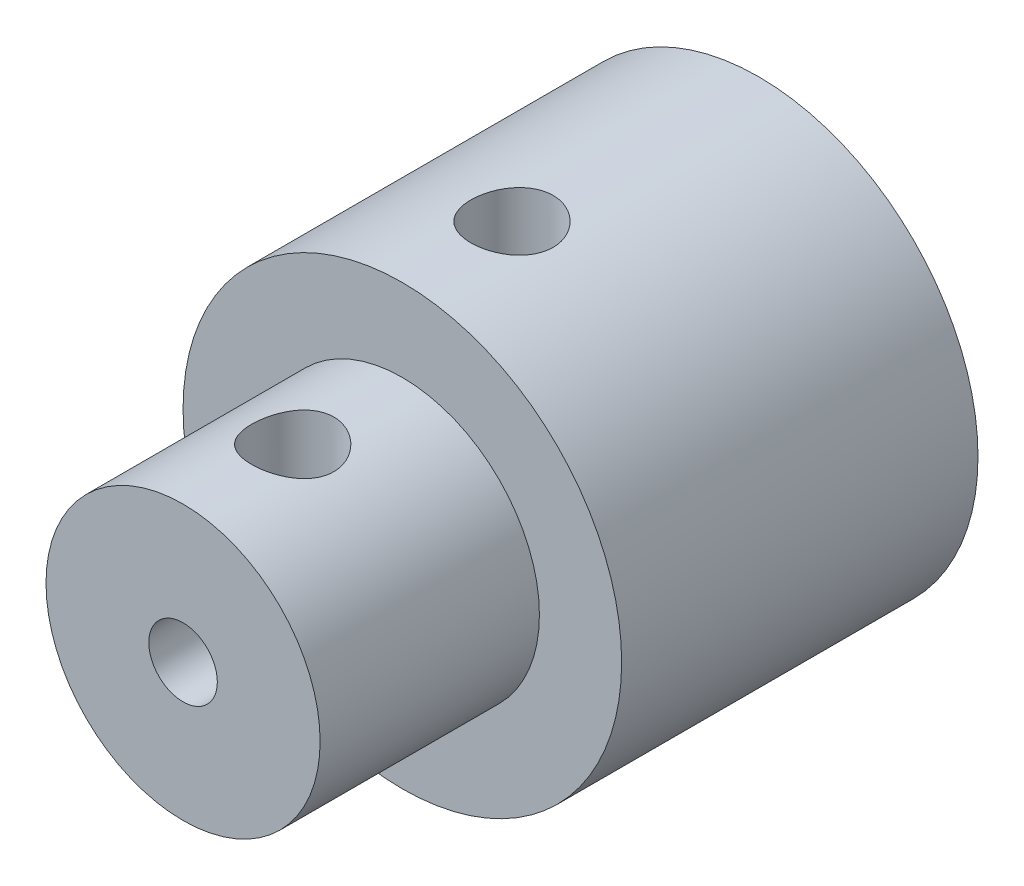
SolidWorks part; units mm, degrees
material "1060 Alloy"
ref_plane "Front Plane" through (0, 0, 0) normal (0, 0, 1) x (1, 0, 0)
ref_plane "Top Plane" through (0, 0, 0) normal (0, 1, 0) x (1, 0, 0)
ref_plane "Right Plane" through (0, 0, 0) normal (1, 0, 0) x (0, 0, -1)
sketch "Sketch1" plane through (0, 0, 0) normal (1, 0, 0) x (0, 0, -1)
  line L0 (0, 0) -> (0, 5)
  line L1 (8, 5) -> (0, 5)
  line L2 (8, 5) -> (8, 8)
  line L3 (8.5772, 0) -> (10.5, 3.2)
  line L4 (10.5, 3.2) -> (21, 3.2)
  line L5 (8, 8) -> (21, 8)
  line L6 (21, 3.2) -> (21, 8)
  line L7 (8.5772, 0) -> (0, 0)
  dimension "D1" = 8
  dimension "D3" = 3.2
  dimension "D4" = 2.5
  dimension "D5" = 13
  dimension "D6" = 8
  dimension "D7" = 121
  dimension "D8" = 5
revolve "Revolve1" add sketch "Sketch1" angle 360 about L7
sketch "Sketch2" plane through (0, 0, 0) normal (0, 1, 0) x (1, 0, 0)
  line L0 (-5, 8) -> (5, 8) construction
  line L1 (-8, 8) -> (8, 8) construction
  circle A0 centre (0, 12) radius 1.5
  circle A1 centre (0, 4) radius 1.5
  dimension "D2" = 3
  dimension "D3" = 3
  dimension "D1" = 4
  dimension "D4" = 4
extrude "Cut-Extrude1" cut sketch "Sketch2" against normal up to next and the other way up to next
sketch "Sketch4" plane through (0, 0, 0) normal (0, 0, 1) x (1, 0, 0)
  circle A0 centre (0, 0) radius 1.25
  dimension "D1" = 2.5
extrude "Cut-Extrude2" cut sketch "Sketch4" against normal blind 10
